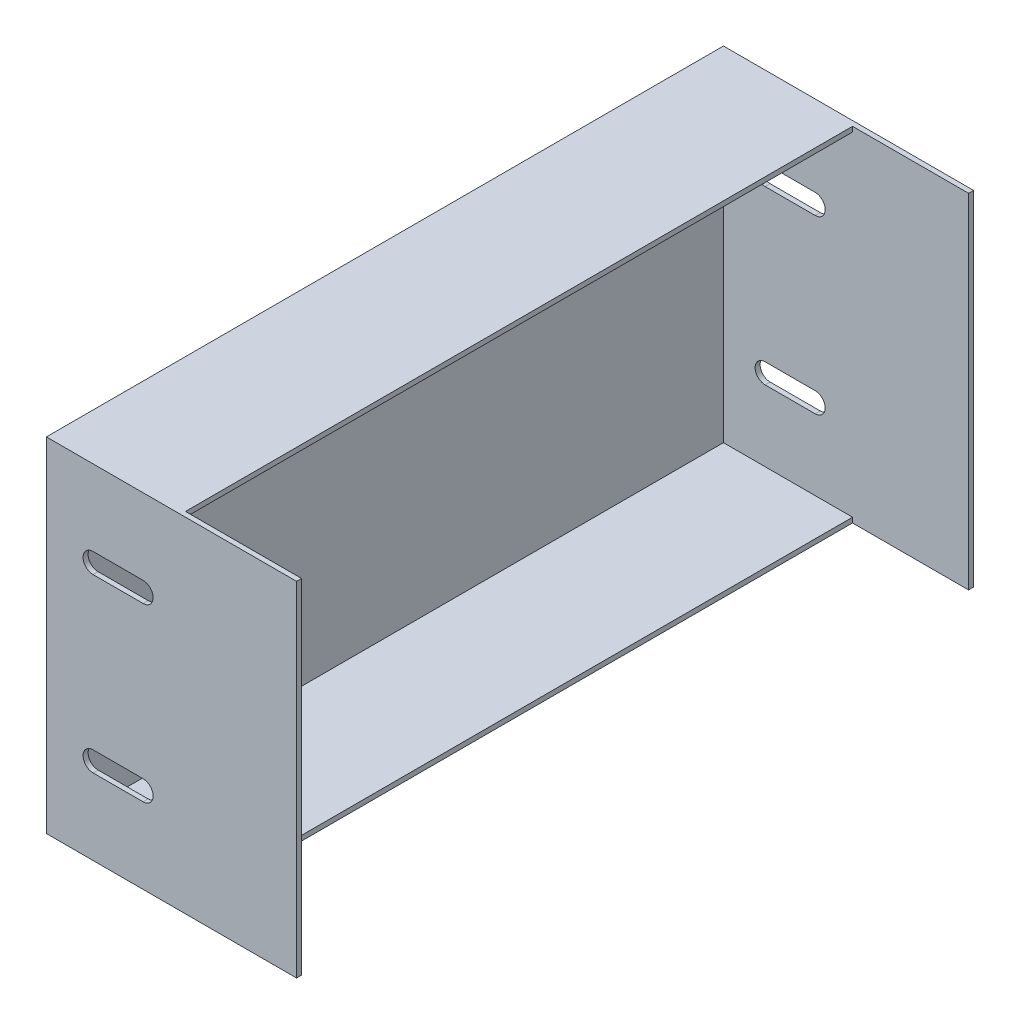
SolidWorks part; units mm, degrees
material "Plain Carbon Steel"
ref_plane "Front Plane" through (0, 0, 0) normal (0, 0, 1) x (1, 0, 0)
ref_plane "Top Plane" through (0, 0, 0) normal (0, 1, 0) x (1, 0, 0)
ref_plane "Right Plane" through (0, 0, 0) normal (1, 0, 0) x (0, 0, -1)
sketch "Sketch1" plane through (0, 0, 0) normal (1, 0, 0) x (0, -1, 0)
  line L2 (50, 100) -> (50, -100)
  line L3 (-50, 100) -> (-50, -100)
  line L5 (50, -100) -> (-50, -100)
  line L11 (50, 100) -> (-50, 100)
  point P1 (50, 0)
  point P3 (0, -100)
  dimension "Width" = 200
extrude "Extrude-Thin1" add sketch "Sketch1" along normal blind 75 thin thin type one direction wall 1.5
sketch "Sketch2" plane through (0, 0, 0) normal (1, 0, 0) x (0, 0, -1)
  line L0 (-101.5, 51.5) -> (-101.5, -51.5)
  line L2 (101.5, 51.5) -> (101.5, -51.5)
  line L3 (-101.5, 51.5) -> (101.5, 51.5)
  line L8 (101.5, -51.5) -> (-101.5, -51.5)
extrude "Boss-Extrude2" add sketch "Sketch2" along normal blind 1.5
sketch "Sketch3" plane through (0, 0, 0) normal (0, 0, 1) x (1, 0, 0)
  line L0 (14, 25.75) -> (29, 25.75) construction
  line L1 (14, 28.75) -> (29, 28.75)
  line L2 (14, 22.75) -> (29, 22.75)
  line L3 (14, -25.75) -> (29, -25.75) construction
  line L4 (14, -22.75) -> (29, -22.75)
  line L5 (14, -28.75) -> (29, -28.75)
  line L6 (1.5, 0) -> (41.5, 0) construction
  line L7 (1.5, -50) -> (1.5, 50) construction
  line L8 (75, 51.5) -> (0, 51.5) construction
  line L9 (21.5, -51.5) -> (21.5, 0) construction
  line L11 (21.5, 0) -> (21.5, 51.5) construction
  arc A0 (14, 28.75) -> (14, 22.75) centre (14, 25.75) ccw
  arc A1 (29, 22.75) -> (29, 28.75) centre (29, 25.75) ccw
  arc A2 (14, -22.75) -> (14, -28.75) centre (14, -25.75) ccw
  arc A3 (29, -28.75) -> (29, -22.75) centre (29, -25.75) ccw
  point P2 (21.5, 25.75)
  point P8 (21.5, -25.75)
  point P22 (1.5, 0)
  dimension "D1" = 3
  dimension "D2" = 15
  dimension "D3" = 40
extrude "Cut-Extrude1" cut sketch "Sketch3" against normal through all and the other way through all
sketch "Sketch4" plane through (-50, 0, 0) normal (0, -1, 0) x (0, 0, -1)
  line L1 (100, 125) -> (-100, 125)
  line L5 (100, 125) -> (100, 90.2006)
  line L6 (100, 90.2006) -> (-100, 90.2006)
  line L7 (-100, 125) -> (-100, 90.2006)
  dimension "D1" = 34.7994
extrude "Cut-Extrude2" cut sketch "Sketch4" against normal through all both and the other way through all
sketch "Sketch5" plane through (75, 0, 0) normal (0, -1, 0) x (-1, 0, 0)
  line L0 (73.5, -100) -> (73.5, 100) construction
  point P1 (73.5, 0)
other "CPoint1" parameters "Diameter"=10, "StubLength"=100
ref_axis "Axis1" through (11.5, 0, 0) along (-1, 0, 0)
equation "\"Length@Extrude-Thin1\"=0.75*\"Height@Sketch1\""
equation "\"Thickness@Boss-Extrude2\"=\"Thickness@Extrude-Thin1\""
